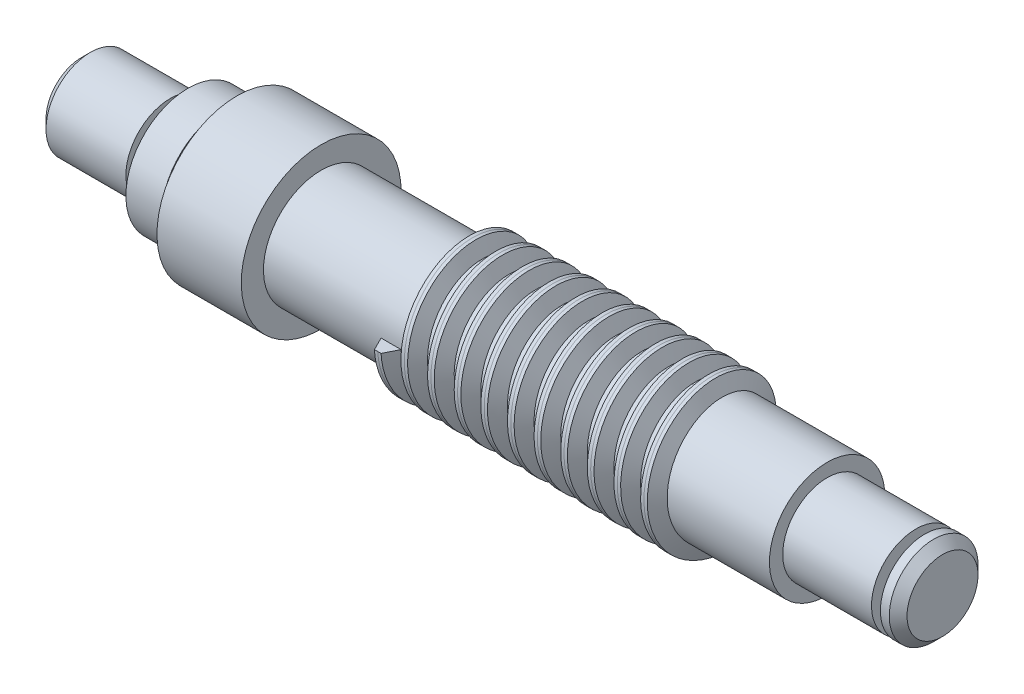
SolidWorks part; units mm, degrees
ref_plane "Plan de face" through (0, 0, 0) normal (0, 0, 1) x (1, 0, 0)
ref_plane "Plan de dessus" through (0, 0, 0) normal (0, 1, 0) x (1, 0, 0)
ref_plane "Plan de droite" through (0, 0, 0) normal (1, 0, 0) x (0, 0, -1)
sketch "Sketch1" plane through (0, 0, 0) normal (0, 0, 1) x (1, 0, 0)
  line L0 (0, 0) -> (0, 2.5)
  line L1 (0, 2.5) -> (-1, 2.5)
  line L2 (-1, 2.5) -> (-1, 1.5)
  line L3 (-1, 1.5) -> (-1.5, 1.5)
  line L4 (-1.5, 1.5) -> (-1.5, 2.5)
  line L5 (-1.5, 2.5) -> (-6.5, 2.5)
  line L6 (-6.5, 2.5) -> (-6.5, 3.25)
  line L7 (-6.5, 3.25) -> (-10.5, 3.25)
  line L11 (-26.5, 3.25) -> (-35, 3.25)
  line L12 (-35, 3.25) -> (-35, 4.5)
  line L13 (-35, 4.5) -> (-39.75, 4.5)
  line L14 (-39.75, 4.5) -> (-39.75, 3)
  line L15 (-39.75, 3) -> (-40.5, 3)
  line L16 (-40.5, 3) -> (-40.5, 3.5)
  line L17 (-40.5, 3.5) -> (-42.5, 3.5)
  line L18 (-42.5, 3.5) -> (-42.5, 2)
  line L19 (-42.5, 2) -> (-43.5, 2)
  line L20 (-43.5, 2) -> (-43.5, 2.5)
  line L21 (-43.5, 2.5) -> (-48.5, 2.5)
  line L22 (-48.5, 2.5) -> (-48.5, 0)
  line L23 (0, 0) -> (-48.5, 0)
  line L24 (-26.5, 3.25) -> (-10.5, 3.25)
  dimension "D1" = 2.5
  dimension "D2" = 1
  dimension "D20" = 1
  dimension "D3" = 1
  dimension "D4" = 0.5
  dimension "D5" = 5
  dimension "D6" = 0.75
  dimension "D7" = 4
  dimension "D8" = 16
  dimension "D9" = 1
  dimension "D12" = 8.5
  dimension "D13" = 1.25
  dimension "D14" = 4.75
  dimension "D15" = 1.5
  dimension "D16" = 0.75
  dimension "D17" = 0.5
  dimension "D18" = 2
  dimension "D19" = 1.5
  dimension "D21" = 0.5
  dimension "D22" = 5
revolve "Revolve1" add sketch "Sketch1" angle 360 about L23
cosmetic thread "Cosmetic Thread1" parameters "D1"=5, "D2"=4
chamfer "Chamfer1" distance 0.5 angle 45 2 edges at (0, 2.5, 0) (-48.5, 2.5, 0)
sketch "Sketch3" plane through (0, 0, 0) normal (0, 0, 1) x (1, 0, 0)
  line L0 (0, 0) -> (-12.0625, 0) construction
  line L1 (-12.0625, 0) -> (-12.0625, 3.25) construction
  line L2 (-6.5, 3.25) -> (-35, 3.25) construction
  dimension "D1" = 12.0625
ref_plane "Plane1" through (-12.0625, 0, 0) normal (-1, 0, 0) x (0, 0, 1)
sketch "Sketch2" plane through (-12.0625, 0, 0) normal (1, 0, 0) x (0, 0, -1)
  circle A0 centre (0, 0) radius 4
  dimension "D1" = 8
curve "Helix/Spiral1" pitch 1.5 height 15.75 radius 4 centre (-12.0625, 0, 0) axis (-1, 0, 0) start towards (0, 0, -1)
sketch "Sketch4" plane through (0, 0, 0) normal (0, 1, 0) x (1, 0, 0)
  line L1 (-12.0625, 4) -> (-12.25, 4)
  line L4 (-6.5, 3.25) -> (-35, 3.25) construction
  line L6 (-12.625, 3.25) -> (-12.25, 4)
  line L12 (-12.0625, 4) -> (-11.875, 4)
  line L13 (-11.875, 4) -> (-11.5, 3.25)
  line L14 (-12.625, 3.25) -> (-12.625, 3)
  line L16 (-11.5, 3) -> (-11.5, 3.25)
  line L17 (-11.5, 3) -> (-12.625, 3)
  spline S0 degree 3 poles (-12.0625, 4) (-12.0936, 4) (-12.1563, 3.7917) (-12.25, 2.9021) (-12.3438, 1.5706) (-12.4375, 0) (-12.5313, -1.5706) (-12.625, -2.9021) (-12.7188, -3.7917) (-12.8125, -4.1041) (-12.9063, -3.7917) (-13, -2.9021) (-13.125, -1.1268) (-13.25, 1.1268) (-13.375, 2.9021) (-13.4688, 3.7917) (-13.5625, 4.1041) (-13.6563, 3.7917) (-13.75, 2.9021) (-13.875, 1.1268) (-14, -1.1268) (-14.125, -2.9021) (-14.2188, -3.7917) (-14.3125, -4.1041) (-14.4063, -3.7917) (-14.5, -2.9021) (-14.625, -1.1268) (-14.75, 1.1268) (-14.875, 2.9021) (-14.9688, 3.7917) (-15.0625, 4.1041) (-15.1563, 3.7917) (-15.25, 2.9021) (-15.375, 1.1268) (-15.5, -1.1268) (-15.625, -2.9021) (-15.7188, -3.7917) (-15.8125, -4.1041) (-15.9063, -3.7917) (-16, -2.9021) (-16.125, -1.1268) (-16.25, 1.1268) (-16.375, 2.9021) (-16.4688, 3.7917) (-16.5625, 4.1041) (-16.6563, 3.7917) (-16.75, 2.9021) (-16.875, 1.1268) (-17, -1.1268) (-17.125, -2.9021) (-17.2188, -3.7917) (-17.3125, -4.1041) (-17.4063, -3.7917) (-17.5, -2.9021) (-17.625, -1.1268) (-17.75, 1.1268) (-17.875, 2.9021) (-17.9688, 3.7917) (-18.0625, 4.1041) (-18.1563, 3.7917) (-18.25, 2.9021) (-18.375, 1.1268) (-18.5, -1.1268) (-18.625, -2.9021) (-18.7188, -3.7917) (-18.8125, -4.1041) (-18.9063, -3.7917) (-19, -2.9021) (-19.125, -1.1268) (-19.25, 1.1268) (-19.375, 2.9021) (-19.4688, 3.7917) (-19.5625, 4.1041) (-19.6563, 3.7917) (-19.75, 2.9021) (-19.875, 1.1268) (-20, -1.1268) (-20.125, -2.9021) (-20.2188, -3.7917) (-20.3125, -4.1041) (-20.4063, -3.7917) (-20.5, -2.9021) (-20.625, -1.1268) (-20.75, 1.1268) (-20.875, 2.9021) (-20.9688, 3.7917) (-21.0625, 4.1041) (-21.1563, 3.7917) (-21.25, 2.9021) (-21.375, 1.1268) (-21.5, -1.1268) (-21.625, -2.9021) (-21.7188, -3.7917) (-21.8125, -4.1041) (-21.9063, -3.7917) (-22, -2.9021) (-22.125, -1.1268) (-22.25, 1.1268) (-22.375, 2.9021) (-22.4688, 3.7917) (-22.5625, 4.1041) (-22.6563, 3.7917) (-22.75, 2.9021) (-22.875, 1.1268) (-23, -1.1268) (-23.125, -2.9021) (-23.2188, -3.7917) (-23.3125, -4.1041) (-23.4063, -3.7917) (-23.5, -2.9021) (-23.625, -1.1268) (-23.75, 1.1268) (-23.875, 2.9021) (-23.9688, 3.7917) (-24.0625, 4.1041) (-24.1563, 3.7917) (-24.25, 2.9021) (-24.375, 1.1268) (-24.5, -1.1268) (-24.625, -2.9021) (-24.7188, -3.7917) (-24.8125, -4.1041) (-24.9063, -3.7917) (-25, -2.9021) (-25.125, -1.1268) (-25.25, 1.1268) (-25.375, 2.9021) (-25.4688, 3.7917) (-25.5625, 4.1041) (-25.6563, 3.7917) (-25.75, 2.9021) (-25.875, 1.1268) (-26, -1.1268) (-26.125, -2.9021) (-26.2187, -3.7917) (-26.3125, -4.1041) (-26.4062, -3.7917) (-26.5, -2.9021) (-26.625, -1.1268) (-26.75, 1.1268) (-26.875, 2.9021) (-26.9687, 3.7917) (-27.0625, 4.1041) (-27.1562, 3.7917) (-27.25, 2.9021) (-27.3437, 1.5706) (-27.4375, 0) (-27.5312, -1.5706) (-27.625, -2.9021) (-27.7187, -3.7917) (-27.7814, -4) (-27.8125, -4) knots 0 0 0 0 0.005952 0.011905 0.017857 0.02381 0.029762 0.035714 0.041667 0.047619 0.053571 0.059524 0.065476 0.077381 0.083333 0.089286 0.095238 0.10119 0.107143 0.113095 0.125 0.130952 0.136905 0.142857 0.14881 0.154762 0.160714 0.172619 0.178571 0.184524 0.190476 0.196429 0.202381 0.208333 0.220238 0.22619 0.232143 0.238095 0.244048 0.25 0.255952 0.267857 0.27381 0.279762 0.285714 0.291667 0.297619 0.303571 0.315476 0.321429 0.327381 0.333333 0.339286 0.345238 0.35119 0.363095 0.369048 0.375 0.380952 0.386905 0.392857 0.39881 0.410714 0.416667 0.422619 0.428571 0.434524 0.440476 0.446429 0.458333 0.464286 0.470238 0.47619 0.482143 0.488095 0.494048 0.505952 0.511905 0.517857 0.52381 0.529762 0.535714 0.541667 0.553571 0.559524 0.565476 0.571429 0.577381 0.583333 0.589286 0.60119 0.607143 0.613095 0.619048 0.625 0.630952 0.636905 0.64881 0.654762 0.660714 0.666667 0.672619 0.678571 0.684524 0.696429 0.702381 0.708333 0.714286 0.720238 0.72619 0.732143 0.744048 0.75 0.755952 0.761905 0.767857 0.77381 0.779762 0.791667 0.797619 0.803571 0.809524 0.815476 0.821429 0.827381 0.839286 0.845238 0.85119 0.857143 0.863095 0.869048 0.875 0.886905 0.892857 0.89881 0.904762 0.910714 0.916667 0.922619 0.934524 0.940476 0.946429 0.952381 0.958333 0.964286 0.970238 0.97619 0.982143 0.988095 0.994048 1 1 1 1 construction
  dimension "D1" = 0.25
  dimension "D2" = 0.1875
  dimension "D3" = 0.75
  dimension "D6" = 0.375
  dimension "D7" = 0.1875
  dimension "D8" = 0.375
sweep "Sweep2" add profiles "Sketch4" path "Helix/Spiral1"
